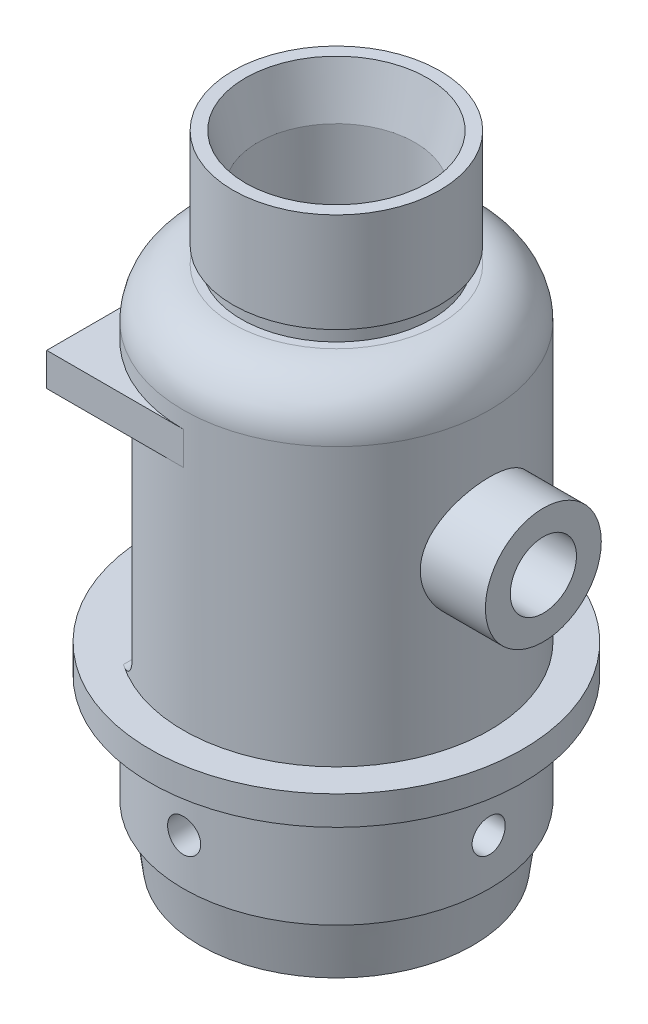
SolidWorks part; units mm, degrees
ref_plane "Front Plane" through (0, 0, 0) normal (0, 0, 1) x (1, 0, 0)
ref_plane "Top Plane" through (0, 0, 0) normal (0, 1, 0) x (1, 0, 0)
ref_plane "Right Plane" through (0, 0, 0) normal (1, 0, 0) x (0, 0, -1)
sketch "Sketch1" plane through (0, 0, 0) normal (0, 0, 1) x (1, 0, 0)
  line L0 (-19, 0) -> (-19, 154)
  line L1 (-19, 154) -> (-25, 154)
  line L2 (-25, 154) -> (-25, 126)
  line L3 (-25, 126) -> (-37, 126)
  line L4 (-37, 126) -> (-37, 47)
  line L5 (-37, 47) -> (-45, 47)
  line L6 (-45, 47) -> (-45, 40)
  line L7 (-45, 40) -> (-37, 40)
  line L8 (-37, 40) -> (-37, 13.8564)
  line L9 (-37, 13.8564) -> (-35, 13.8564)
  line L10 (-35, 13.8564) -> (-33, 0)
  line L11 (-33, 0) -> (-19, 0)
  line L12 (0, 0) -> (0, 98.3724) construction
  dimension "D1" = 19
  dimension "D2" = 33
  dimension "D3" = 35
  dimension "D4" = 37
  dimension "D5" = 45
  dimension "D6" = 28
  dimension "D7" = 7
  dimension "D8" = 40
  dimension "D9" = 154
  dimension "D10" = 14
  dimension "D11" = 25
revolve "Revolve1" add sketch "Sketch1" angle 360 about L12
sketch "Sketch2" plane through (0, 0, 0) normal (0, 0, 1) x (1, 0, 0)
  line L0 (37, 13.8564) -> (37, 40) construction
  line L1 (25, 126) -> (23, 126)
  line L2 (25, 126) -> (25, 130)
  line L3 (25, 130) -> (23, 130)
  line L4 (23, 126) -> (23, 130)
  line L5 (37, 40) -> (32, 40)
  line L6 (37, 40) -> (37, 35.8564)
  line L7 (37, 35.8564) -> (32, 35.8564)
  line L8 (32, 40) -> (32, 35.8564)
  line L9 (-37, 40) -> (37, 40) construction
  line L10 (-35, 13.8564) -> (35, 13.8564) construction
  line L11 (0, 0) -> (0, 96.8202) construction
  dimension "D1" = 4
  dimension "D2" = 22
  dimension "D3" = 32
  dimension "D4" = 23
revolve "Cut-Revolve1" cut sketch "Sketch2" angle 360 about L11
sketch "Sketch3" plane through (0, 0, 0) normal (1, 0, 0) x (0, 0, -1)
  circle A0 centre (0, 86) radius 14
  point P2 (0, 0)
  dimension "D1" = 28
  dimension "D2" = 86
ref_plane "Plane1" through (50, 0, 0) normal (1, 0, 0) x (0, 0, -1)
sketch "Sketch4" plane through (50, 0, 0) normal (1, 0, 0) x (0, 0, -1)
  circle A1 centre (0, 86) radius 14
  circle A2 centre (0, 86) radius 14
  dimension "D1" = 0
extrude "Boss-Extrude2" add sketch "Sketch4" against normal up to next
hole_wizard "Hole1" positions "Sketch5" profile "Sketch6" legacy end condition up to next
sketch "Sketch5" plane through (50, 0, 0) normal (1, 0, 0) x (0, 0, -1)
  point P0 (0, 86)
sketch "Sketch6" plane through (50, 86, 0) normal (0, 1, 0) x (0, 0, -1)
  line L0 (0, 0) -> (0, 31)
  line L1 (0, 31) -> (8, 31)
  line L2 (8, 31) -> (8, 0)
  line L3 (8, 0) -> (0, 0)
  line L4 (0, 110) -> (0, -10) construction
  dimension "Diameter" = 16
  dimension "Depth" = 31
fillet "Fillet1" radius 12 1 edges at (0, 126, -37)
hole_wizard "Hole2" positions "Sketch7" profile "Sketch8" legacy
sketch "Sketch7" plane through (0, 0, 0) normal (0, -1, 0) x (-1, 0, 0)
  point P0 (0, 0)
sketch "Sketch8" plane through (0, 0, 0) normal (1, 0, 0) x (0, 0, -1)
  line L0 (0, 0) -> (0, 119)
  line L1 (0, 119) -> (28, 119)
  line L2 (28, 119) -> (28, 0)
  line L3 (28, 0) -> (0, 0)
  line L4 (0, 110) -> (0, -10) construction
  dimension "Diameter" = 56
  dimension "Depth" = 119
sketch "Sketch11" plane through (0, 0, 0) normal (0, 0, 1) x (1, 0, 0)
  circle A0 centre (0, 25) radius 4
  dimension "D1" = 8
  dimension "D2" = 25
extrude "Cut-Extrude1" cut sketch "Sketch11" against normal through all
pattern_circular "CirPattern1" count 4 over 360 about axis through (0, 0, 0) along (0, -1, 0) of "Cut-Extrude1" reverse direction yes
ref_plane "Plane2" through (0, 102, 0) normal (0, 1, 0) x (1, 0, 0)
sketch "Sketch12" plane through (0, 102, 0) normal (0, 1, 0) x (1, 0, 0)
  line L0 (-33, 37) -> (-33, 16.7332)
  line L1 (0, 37) -> (-33, 37)
  line L2 (0, -37) -> (-33, -37)
  line L3 (-33, -16.7332) -> (-33, -37)
  circle A2 centre (0, 0) radius 37 construction
  arc A3 (0, 37) -> (-33, 16.7332) centre (0, 0) ccw
  arc A4 (-33, -16.7332) -> (0, -37) centre (0, 0) ccw
  dimension "D1" = 33
extrude "Boss-Extrude3" add sketch "Sketch12" along normal blind 8
sketch "Sketch13" plane through (0, 102, 0) normal (0, 1, 0) x (1, 0, 0)
  line L0 (-33, 16.7332) -> (-33, -16.7332)
  circle A0 centre (0, 0) radius 37 construction
  arc A1 (-33, 16.7332) -> (-33, -16.7332) centre (0, 0) ccw
  dimension "D1" = 33
extrude "Cut-Extrude2" cut sketch "Sketch13" along normal through all and the other way up to surface (55 mm away) other way up to face at (0, 47, -45)
sketch "Sketch14" plane through (0, 0, 0) normal (0, 0, 1) x (1, 0, 0)
  line L0 (-33, 102) -> (0, 102) construction
  line L1 (-16, 102) -> (-37, 102)
  line L2 (-16, 102) -> (-16, 47)
  line L3 (-16, 47) -> (-37, 47)
  line L4 (-37, 102) -> (-37, 47)
  line L7 (45, 47) -> (-45, 47) construction
  dimension "D1" = 16
  dimension "D2" = 37
extrude "Cut-Extrude3" cut sketch "Sketch14" against normal mid plane 80
chamfer "Chamfer1" distance 12 distance2 3 1 edges at (0, 154, -19) first distance on face at (0, 119, 19)
fillet "Fillet2" radius 5 4 edges at (-16, 102, -28.17) (-16, 102, 28.17) (-16, 47, 28.17) (-16, 47, -28.17)
fillet "Fillet3" radius 5 1 edges at (0, 119, 19)
